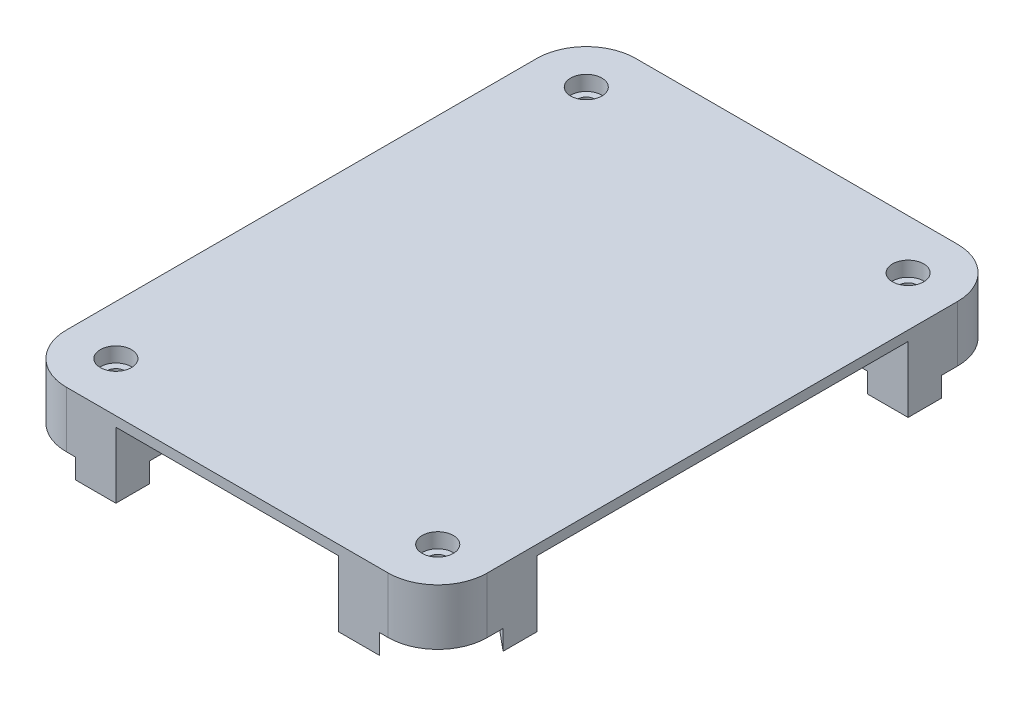
SolidWorks part; units mm, degrees
note: '?' marks a value the reader was unsure of.
material "3-D Printed ABS"
ref_plane "Front Plane" through (0, 0, 0) normal (0, 0, 1) x (1, 0, 0)
ref_plane "Top Plane" through (0, 0, 0) normal (0, 1, 0) x (1, 0, 0)
ref_plane "Right Plane" through (0, 0, 0) normal (1, 0, 0) x (0, 0, -1)
sketch "Sketch1" plane through (0, 0, 0) normal (0, 1, 0) x (1, 0, 0)
  line L1 (-53.975, -73.025) -> (53.975, -73.025)
  line L2 (-53.975, -73.025) -> (-53.975, 73.025)
  line L3 (-53.975, 73.025) -> (53.975, 73.025)
  line L4 (53.975, -73.025) -> (53.975, 73.025)
  line L5 (-53.975, -73.025) -> (53.975, 73.025) construction
  line L6 (-53.975, 73.025) -> (53.975, -73.025) construction
  point P0 (0, 0)
  dimension "D1" = 107.95
  dimension "D2" = 146.05
extrude "Boss-Extrude1" add sketch "Sketch1" against normal blind 2.54
sketch "Sketch13" plane through (0, 0, 0) normal (0, 1, 0) x (1, 0, 0)
  line L0 (0, 155.0212) -> (0, -155.0212) construction
  line L1 (0, 0) -> (-92.0171, 0) construction
  line L2 (53.975, -73.025) -> (53.975, 73.025) construction
  line L3 (53.975, -73.025) -> (28.575, -73.025)
  line L4 (53.975, -73.025) -> (53.975, -47.625)
  line L5 (53.975, -47.625) -> (28.575, -47.625)
  line L6 (28.575, -73.025) -> (28.575, -47.625)
  line L7 (-53.975, -73.025) -> (53.975, -73.025) construction
  line L8 (-28.575, -73.025) -> (-28.575, -47.625)
  line L9 (-53.975, -47.625) -> (-28.575, -47.625)
  line L10 (-53.975, -73.025) -> (-53.975, -47.625)
  line L11 (-53.975, -73.025) -> (-28.575, -73.025)
  line L12 (-53.975, 73.025) -> (-28.575, 73.025)
  line L13 (-53.975, 73.025) -> (-53.975, 47.625)
  line L14 (-53.975, 47.625) -> (-28.575, 47.625)
  line L15 (-28.575, 73.025) -> (-28.575, 47.625)
  line L16 (28.575, 73.025) -> (28.575, 47.625)
  line L17 (53.975, 47.625) -> (28.575, 47.625)
  line L18 (53.975, 73.025) -> (53.975, 47.625)
  line L19 (53.975, 73.025) -> (28.575, 73.025)
  dimension "D1" = 25.4
  dimension "D2" = 25.4
extrude "Boss-Extrude4" add sketch "Sketch13" against normal blind 19.431
sketch "Sketch2" plane through (0, 0, 0) normal (0, 1, 0) x (1, 0, 0)
  line L0 (0, 0) -> (100.1618, 0) construction
  line L1 (0, 0) -> (0, 86.3534) construction
  line L2 (-53.975, 73.025) -> (-53.975, -73.025) construction
  line L3 (53.975, 73.025) -> (-53.975, 73.025) construction
  line L4 (0, 0) -> (-53.975, 73.025) construction
  circle A0 centre (-41.275, 60.325) radius 3.302
  circle A1 centre (41.275, 60.325) radius 3.302
  circle A2 centre (41.275, -60.325) radius 3.302
  circle A3 centre (-41.275, -60.325) radius 3.302
  dimension "D1" = 6.604
  dimension "D3" = 12.7
  dimension "D2" = 12.7
extrude "Cut-Extrude1" cut sketch "Sketch2" against normal through all
sketch "Sketch3" plane through (0, 0, 0) normal (0, 1, 0) x (1, 0, 0)
  line L0 (-53.975, 25.4) -> (53.975, 25.4) construction
  line L1 (-23.495, 60.325) -> (-19.05, 60.325)
  line L2 (-23.495, 60.325) -> (-23.495, 44.45)
  line L3 (-23.495, 44.45) -> (-19.05, 44.45)
  line L4 (-19.05, 60.325) -> (-19.05, 44.45)
  line L5 (19.05, 60.325) -> (19.05, 44.45)
  line L6 (23.495, 44.45) -> (19.05, 44.45)
  line L7 (23.495, 60.325) -> (23.495, 44.45)
  line L8 (23.495, 60.325) -> (19.05, 60.325)
  line L9 (-53.975, 73.025) -> (-53.975, -73.025) construction
  line L10 (53.975, -73.025) -> (53.975, 73.025) construction
  line L11 (0, 0) -> (0, 97.7255) construction
  line L12 (0, 50.8) -> (0, -46.9255) construction
  line L13 (23.495, -9.525) -> (19.05, -9.525)
  line L14 (23.495, -9.525) -> (23.495, 6.35)
  line L15 (23.495, 6.35) -> (19.05, 6.35)
  line L16 (19.05, -9.525) -> (19.05, 6.35)
  line L17 (-19.05, -9.525) -> (-19.05, 6.35)
  line L18 (-23.495, 6.35) -> (-19.05, 6.35)
  line L19 (-23.495, -9.525) -> (-23.495, 6.35)
  line L20 (-23.495, -9.525) -> (-19.05, -9.525)
  dimension "D1" = 15.875
  dimension "D2" = 4.445
  dimension "D3" = 19.05
  dimension "D4" = 25.4
  dimension "D5" = 44.45
extrude "Cut-Extrude2" [suppressed] cut sketch "Sketch3" against normal through all
fillet "Fillet1" radius 12.7 4 edges at (53.975, -9.7155, -73.025) (53.975, -9.7155, 73.025) (-53.975, -9.7155, 73.025) (-53.975, -9.7155, -73.025)
sketch "Sketch4" plane through (0, 0, 0) normal (0, 1, 0) x (1, 0, 0)
  line L0 (0, 0) -> (80.9727, -80.9727) construction
  line L1 (0, 0) -> (-80.9727, -80.9727) construction
  line L2 (69.1118, -51.1513) -> (28.7006, -10.7401)
  line L3 (28.7006, -10.7401) -> (10.7401, -28.7006)
  line L4 (10.7401, -28.7006) -> (51.1513, -69.1118)
  line L5 (51.1513, -69.1118) -> (69.1118, -51.1513)
  line L6 (0, 0) -> (0, -118.7381) construction
  line L7 (0, 0) -> (-98.4177, 0) construction
  line L8 (-51.1513, -69.1118) -> (-69.1118, -51.1513)
  line L9 (-69.1118, -51.1513) -> (-28.7006, -10.7401)
  line L10 (-28.7006, -10.7401) -> (-10.7401, -28.7006)
  line L11 (-10.7401, -28.7006) -> (-51.1513, -69.1118)
  line L12 (-69.1118, 51.1513) -> (-28.7006, 10.7401)
  line L13 (-51.1513, 69.1118) -> (-69.1118, 51.1513)
  line L14 (-10.7401, 28.7006) -> (-51.1513, 69.1118)
  line L15 (-28.7006, 10.7401) -> (-10.7401, 28.7006)
  line L16 (51.1513, 69.1118) -> (69.1118, 51.1513)
  line L17 (69.1118, 51.1513) -> (28.7006, 10.7401)
  line L18 (28.7006, 10.7401) -> (10.7401, 28.7006)
  line L19 (10.7401, 28.7006) -> (51.1513, 69.1118)
  point P6 (19.7204, -19.7204)
  dimension "D1" = 25.4
  dimension "D2" = 57.15
  dimension "D3" = 45
extrude "Cut-Extrude3" [suppressed] cut sketch "Sketch4" against normal blind 1.5875
sketch "Sketch6" [suppressed] plane through (0, 0, 0) normal (0, 1, 0) x (1, 0, 0)
  line L0 (46.3377, -44.1074) -> (34.6634, -32.4331) construction
  line L1 (0, 0) -> (0, -117.7376) construction
  line L2 (0, 0) -> (-151.7285, 0) construction
  line L4 (28.1601, -10.1996) -> (10.1996, -28.1601) construction
  line L5 (50.6107, -68.5712) -> (68.5712, -50.6107) construction
  text T0 "ESC" font "Century Gothic" height in points 22
  dimension "D1" = 45
  dimension "D2" = 20.32
  dimension "D3" = 20.32
extrude "Cut-Extrude5" [suppressed] cut sketch "Sketch6" against normal blind 3.175
sketch "Sketch5" plane through (0, 0, 0) normal (0, 1, 0) x (1, 0, 0)
  line L0 (41.275, 73.025) -> (-41.275, 73.025) construction
  line L1 (14.2875, 15.875) -> (-14.2875, 15.875)
  line L2 (14.2875, 15.875) -> (14.2875, 66.675)
  line L3 (14.2875, 66.675) -> (-14.2875, 66.675)
  line L4 (-14.2875, 15.875) -> (-14.2875, 66.675)
  point P4 (0, 15.875)
  dimension "D1" = 50.8
  dimension "D2" = 28.575
  dimension "D3" = 6.35
extrude "Cut-Extrude4" [suppressed] cut sketch "Sketch5" against normal blind 1.5875
ref_axis "Axis1" through (0, 0.3175, 0) along (0, -1, 0)?
pattern_circular "CirPattern1" [suppressed] count 4 over 360 about axis through (0, 0.3175, 0) along (0, -1, 0)
sketch "Sketch7" plane through (0, 0, 0) normal (0, 1, 0) x (1, 0, 0)
  line L0 (0, 0) -> (0, -54.962) construction
  line L1 (63.4018, -13.3522) -> (38.0018, -13.3522)
  line L2 (63.4018, -13.3522) -> (63.4018, 43.7978)
  line L3 (63.4018, 43.7978) -> (38.0018, 43.7978)
  line L4 (38.0018, -13.3522) -> (38.0018, 43.7978)
  line L5 (-38.0018, -13.3522) -> (-38.0018, 43.7978)
  line L6 (-63.4018, 43.7978) -> (-38.0018, 43.7978)
  line L7 (-63.4018, -13.3522) -> (-63.4018, 43.7978)
  line L8 (-63.4018, -13.3522) -> (-38.0018, -13.3522)
  line L9 (-41.275, -73.025) -> (41.275, -73.025) construction
  line L10 (38.5677, -40.64) -> (-18.5823, -40.64)
  line L11 (38.5677, -40.64) -> (38.5677, -66.04)
  line L12 (38.5677, -66.04) -> (-18.5823, -66.04)
  line L13 (-18.5823, -40.64) -> (-18.5823, -66.04)
  line L14 (38.5677, -40.64) -> (-18.5823, -66.04) construction
  line L15 (38.5677, -66.04) -> (-18.5823, -40.64) construction
  line L16 (19.844, -36.1003) -> (-37.306, -36.1003)
  line L17 (19.844, -36.1003) -> (19.844, -61.5003)
  line L18 (19.844, -61.5003) -> (-37.306, -61.5003)
  line L19 (-37.306, -36.1003) -> (-37.306, -61.5003)
  line L20 (19.844, -36.1003) -> (-37.306, -61.5003) construction
  line L21 (19.844, -61.5003) -> (-37.306, -36.1003) construction
  point P11 (9.9927, -53.34)
  point P18 (-8.731, -48.8003)
  dimension "D1" = 57.15
  dimension "D2" = 25.4
  dimension "D3" = 57.15
  dimension "D4" = 25.4
  dimension "D5" = 6.985
  dimension "D6" = 57.15
  dimension "D7" = 25.4
extrude "Cut-Extrude6" [suppressed] cut sketch "Sketch7" against normal blind 1.27
sketch "Sketch8" plane through (0, 0, 0) normal (0, 1, 0) x (1, 0, 0)
  line L7 (19.05, -31.75) -> (-19.05, -31.75)
  line L8 (19.05, -31.75) -> (19.05, 31.75)
  line L9 (19.05, 31.75) -> (-19.05, 31.75)
  line L10 (-19.05, -31.75) -> (-19.05, 31.75)
  point P0 (0, 0)
  dimension "D1" = 38.1
  dimension "D2" = 31.75
  dimension "D3" = 63.5
extrude "Boss-Extrude3" [suppressed] add sketch "Sketch8" along normal blind 2.54
sketch "Sketch11" plane through (0, 0, 0) normal (0, 1, 0) x (1, 0, 0)
  line L1 (19.05, -9.525) -> (-19.05, -9.525)
  line L2 (19.05, -9.525) -> (19.05, 6.35)
  line L3 (19.05, 6.35) -> (-19.05, 6.35)
  line L4 (-19.05, -9.525) -> (-19.05, 6.35)
extrude "Cut-Extrude9" [suppressed] cut sketch "Sketch11" against normal mid plane 2.54
sketch "Sketch12" [suppressed] plane through (0, 0, 0) normal (0, 1, 0) x (1, 0, 0)
  line L0 (-23.495, -9.525) -> (-19.05, -9.525) construction
  line L1 (12.7, -9.525) -> (-12.7, -9.525)
  line L2 (12.7, -9.525) -> (12.7, 6.35)
  line L3 (12.7, 6.35) -> (-12.7, 6.35)
  line L4 (-12.7, -9.525) -> (-12.7, 6.35)
  line L5 (-19.05, 6.35) -> (-23.495, 6.35) construction
  line L6 (19.05, 52.3875) -> (-19.05, 52.3875) construction
  line L7 (19.05, 60.325) -> (19.05, 44.45) construction
  line L8 (-19.05, 44.45) -> (-19.05, 60.325) construction
  line L9 (-12.7, 114.3) -> (-12.7, 98.425)
  line L10 (12.7, 98.425) -> (-12.7, 98.425)
  line L11 (12.7, 114.3) -> (12.7, 98.425)
  line L12 (12.7, 114.3) -> (-12.7, 114.3)
  point P8 (0, -9.525)
  dimension "D1" = 25.4
extrude "Cut-Extrude12" [suppressed] cut sketch "Sketch12" along normal through all
sketch "Sketch9" plane through (0, 0, 0) normal (0, 1, 0) x (1, 0, 0)
  line L1 (25.1579, -52.4084) -> (-25.6421, -52.4084)
  line L2 (25.1579, -52.4084) -> (25.1579, -1.6084)
  line L3 (25.1579, -1.6084) -> (-25.6421, -1.6084)
  line L4 (-25.6421, -52.4084) -> (-25.6421, -1.6084)
  line L5 (25.1579, -52.4084) -> (-25.6421, -1.6084) construction
  line L6 (25.1579, -1.6084) -> (-25.6421, -52.4084) construction
  point P0 (-0.2421, -27.0084)
  dimension "D1" = 50.8
  dimension "D2" = 50.8
fillet "Fillet2" [suppressed] radius 12.7
sketch "Sketch14" plane through (0, -19.431, 0) normal (0, -1, 0) x (1, 0, 0)
  line L0 (0, 0) -> (0, -152.4) construction
  line L1 (0, 0) -> (152.4, 0) construction
  line L2 (0, 0) -> (152.4, -152.4) construction
  line L3 (152.4, -152.4) -> (41.275, -60.325) construction
  line L4 (41.275, -60.325) -> (27.042, -48.5319) construction
  line L5 (27.042, -48.5319) -> (0, -26.1257) construction
  line L6 (20.692, -28.6742) -> (6.35, -45.9835)
  line L7 (6.35, -45.9835) -> (139.337, -156.1727)
  line L8 (139.337, -156.1727) -> (153.679, -138.8634)
  line L9 (153.679, -138.8634) -> (20.692, -28.6742)
  line L10 (-20.692, -28.6742) -> (-6.35, -45.9835)
  line L11 (-153.679, -138.8634) -> (-20.692, -28.6742)
  line L12 (-6.35, -45.9835) -> (-139.337, -156.1727)
  line L13 (-139.337, -156.1727) -> (-153.679, -138.8634)
  line L14 (-153.679, 138.8634) -> (-20.692, 28.6742)
  line L15 (-139.337, 156.1727) -> (-153.679, 138.8634)
  line L16 (-6.35, 45.9835) -> (-139.337, 156.1727)
  line L17 (-20.692, 28.6742) -> (-6.35, 45.9835)
  line L18 (20.692, 28.6742) -> (6.35, 45.9835)
  line L19 (139.337, 156.1727) -> (153.679, 138.8634)
  line L20 (153.679, 138.8634) -> (20.692, 28.6742)
  line L21 (6.35, 45.9835) -> (139.337, 156.1727)
  point P3 (13.521, -37.3288)
  point P6 (41.275, -60.325)
  dimension "D1" = 152.4
  dimension "D2" = 152.4
  dimension "D3" = 6.35
  dimension "D4" = 11.2395
extrude "Cut-Extrude13" cut sketch "Sketch14" against normal blind 5.08
sketch "Sketch15" plane through (0, 0, 0) normal (0, 1, 0) x (1, 0, 0)
  line L0 (0, 0) -> (72.5178, 0) construction
  line L1 (0, 0) -> (0, 124.598) construction
  circle A0 centre (-41.275, 60.325) radius 6.35
  circle A1 centre (41.275, 60.325) radius 6.35
  circle A2 centre (-41.275, -60.325) radius 6.35
  circle A3 centre (41.275, -60.325) radius 6.35
extrude "Boss-Extrude5" add sketch "Sketch15" against normal offset from surface (11.811 mm away) 2.54 up to face at (-41.6508, -14.351, -60.7008)
hole_wizard "M4 Clearance Hole1" [suppressed] positions "Sketch18" profile "Sketch16" hole size "M4" standard "ANSI Metric"
sketch "Sketch18" plane through (0, -19.05, 0) normal (0, -1, 0) x (-1, 0, 0)
  point P0 (41.275, 60.325)
  point P3 (41.275, -60.325)
  point P6 (-41.275, -60.325)
  point P9 (-41.275, 60.325)
sketch "Sketch16" plane through (-41.275, -19.05, -60.325) normal (1, 0, 0) x (0, 0, -1)
  line L0 (0, 0) -> (0, 19.05)
  line L1 (0, 19.05) -> (2.25, 19.05)
  line L2 (2.25, 19.05) -> (2.25, 0)
  line L5 (2.25, 0) -> (0, 0)
  line L11 (0, -6.35) -> (0, 107.95) construction
  dimension "Thru Hole Dia." = 4.5
  dimension "Thru Hole Depth" = 19.05
hole_wizard "CBORE for M4 SHCS1" [suppressed] positions "Sketch21" profile "Sketch20" counterbore size "M4" standard "ANSI Metric"
sketch "Sketch21" [suppressed] plane through (0, 0, 0) normal (0, 1, 0) x (1, 0, 0)
  point P0 (41.275, 60.325)
  point P3 (-41.275, 60.325)
  point P6 (-41.275, -60.325)
  point P9 (41.275, -60.325)
sketch "Sketch20" plane through (41.275, 0, -60.325) normal (1, 0, 0) x (0, 0, 1)
  line L0 (0, 0) -> (0, 24.13)
  line L1 (0, 24.13) -> (2.25, 24.13)
  line L3 (2.25, 24.13) -> (2.25, 4)
  line L4 (2.25, 4) -> (4, 4)
  line L5 (4, 4) -> (4, 0)
  line L7 (4, 0) -> (0, 0)
  line L11 (0, -6.35) -> (0, 107.95) construction
  dimension "Thru Hole Dia." = 4.5
  dimension "Thru Hole Depth" = 24.13
  dimension "C'Bore Dia." = 8
  dimension "C'Bore Depth" = 4
sketch "Sketch23" plane through (0, -14.351, 0) normal (0, -1, 0) x (1, 0, 0)
  circle A0 centre (-41.275, -60.325) radius 2.25
  dimension "D1" = 4.5
extrude "Cut-Extrude14" cut sketch "Sketch23" against normal through all
sketch "Sketch24" plane through (0, 0, 0) normal (0, 1, 0) x (1, 0, 0)
  circle A0 centre (-41.275, 60.325) radius 4
  dimension "D1" = 8
extrude "Cut-Extrude15" cut sketch "Sketch24" against normal blind 3.81
mirror "Mirror1" about plane through (0, 0, 0) normal (0, 0, 1) of "Cut-Extrude15", "Cut-Extrude14"
mirror "Mirror2" about plane through (0, 0, 0) normal (1, 0, 0) of "Cut-Extrude15", "Cut-Extrude14", "Mirror1"
fillet "Fillet3" radius 12.7 4 edges at (-28.575, -8.4455, -47.625) (28.575, -8.4455, -47.625) (28.575, -8.4455, 47.625) (-28.575, -8.4455, 47.625)
sketch "Sketch25" plane through (0, 0, 0) normal (0, 1, 0) x (1, 0, 0)
  line L0 (0, 0) -> (0, -33.9706) construction
  line L1 (0, 0) -> (63.8751, 0) construction
  circle A0 centre (30.0609, 0) radius 3.4925
  circle A1 centre (30.0609, -24.9682) radius 3.4925
  circle A2 centre (30.0609, 24.9682) radius 3.4925
  circle A3 centre (-30.0609, 24.9682) radius 3.4925
  circle A4 centre (-30.0609, -24.9682) radius 3.4925
  circle A5 centre (-30.0609, 0) radius 3.4925
  dimension "D1" = 6.985
  dimension "D2" = 6.985
  dimension "D3" = 24.9682
  dimension "D4" = 30.0609
extrude "GimbalMount1" [suppressed] cut sketch "Sketch25" against normal through all
sketch "Sketch26" [suppressed] plane through (0, 0, 0) normal (0, 1, 0) x (1, 0, 0)
  circle A0 centre (30.0609, -24.9682) radius 5.715
  circle A1 centre (30.0609, 0) radius 5.715
  circle A2 centre (30.0609, 24.9682) radius 5.715
  circle A3 centre (-30.0609, -24.9682) radius 5.715
  circle A4 centre (-30.0609, 0) radius 5.715
  circle A5 centre (-30.0609, 24.9682) radius 5.715
  dimension "D1" = 11.43
extrude "GimbalMount2" [suppressed] cut sketch "Sketch26" against normal blind 1.524
fillet "Fillet4" radius 1.016 4 edges at (41.275, -14.351, 63.627) (-41.275, -14.351, 57.023) (-41.275, -14.351, -57.023) (41.275, -14.351, -63.627)
equation "\"Plate Thickness\"= \"Plate Thickness@Quad Assemb.sldasm\""
equation "\"D1@Boss-Extrude1\"=\"Plate Thickness\""
equation "\"Plate Dim X\"= \"Plate Dim X@Quad Assemb.sldasm\""
equation "\"Plate Dim Y\"= \"Plate Dim Y@Quad Assemb.sldasm\""
equation "\"D1@Boss-Extrude4\"=\"Component Y@Quad Assemb.sldasm\"-\"ArmBase@Arm V3-1.Part\""
equation "\"D4@Sketch14\"=\"ArmBase@Arm V3-1.Part\"/2+.005"
equation "\"Dowell Width\"= \"Dowell Width@Quad Assemb.sldasm\""
equation "\"D1@Sketch2\"=\"Dowell Width\"+.01"
equation "\"Dowell Height\"= \"Dowell Height@Quad Assemb.sldasm\""
equation "\"D1@Boss-Extrude5\"=\"Dowell Height\""
equation "\"GimbalMount1\"= if ( \"Gimbal Mount@Quad Assemb.sldasm\" = 1 , \"unsuppressed\" , \"suppressed\" )"
equation "\"GimbalMount2\"= if ( \"Gimbal Mount@Quad Assemb.sldasm\" = 1 , \"unsuppressed\" , \"suppressed\" )"
